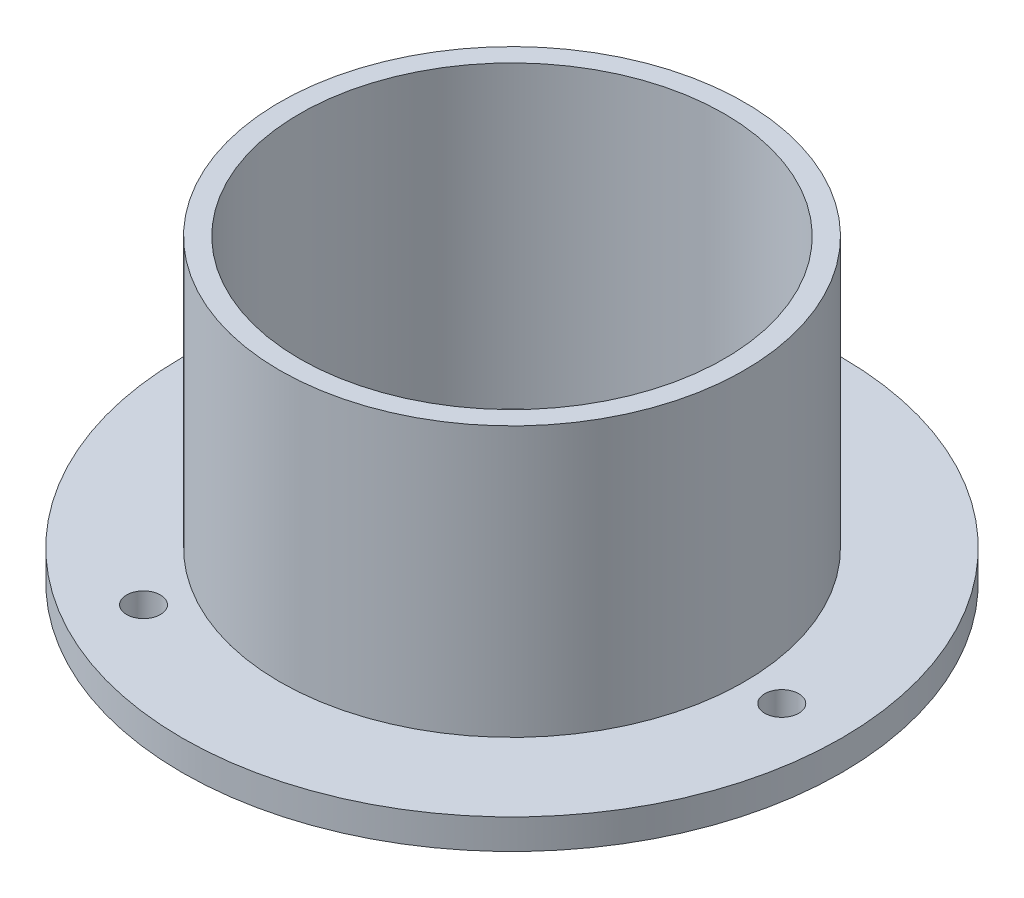
SolidWorks part; units mm, degrees
material "PETG"
ref_plane "Front Plane" through (0, 0, 0) normal (0, 0, 1) x (1, 0, 0)
ref_plane "Top Plane" through (0, 0, 0) normal (0, 1, 0) x (1, 0, 0)
ref_plane "Right Plane" through (0, 0, 0) normal (1, 0, 0) x (0, 0, -1)
sketch "Sketch1" plane through (0, 0, 0) normal (0, 1, 0) x (1, 0, 0)
  circle A2 centre (0, 0) radius 33
  circle A3 centre (0, 0) radius 21.25
  circle A4 centre (0, 0) radius 23.25
  dimension "D1" = 66
  dimension "D2" = 42.5
  dimension "D3" = 46.5
extrude "Boss-Extrude1" add sketch "Sketch1" along normal blind 30 contours A4 A3 region at (-22.5924, 0, 0)
extrude "Boss-Extrude2" add sketch "Sketch1<4>" along normal blind 3 contours A2 A4 region at (-32.0666, 0, 0)
sketch "Sketch1<4>" plane through (0, 0, 0) normal (0, 1, 0) x (1, 0, 0) same geometry as "Sketch1"
sketch "Sketch2" plane through (0, 3, 0) normal (0, 1, 0) x (1, 0, 0)
  circle A0 centre (0, 0) radius 27 construction
  circle A1 centre (27, 0) radius 1.7
  circle A2 centre (-13.5, -23.3827) radius 1.7
  circle A3 centre (0, 0) radius 27 construction
  circle A4 centre (-13.5, 23.3827) radius 1.7
  circle A5 centre (0, 0) radius 27 construction
  point P13 (0, 0)
  dimension "D1" = 54
  dimension "D2" = 3.4
  dimension "D3" = 3
extrude "Cut-Extrude1" cut sketch "Sketch2" against normal through all
equation "\"____ GENERATED PART EXPORTS ____\" = 0"
equation "\"SYS_VersionTag\" = 2"
equation "\"CDG_Enabled\" = 1"
equation "\"CDG_IsStructural\" = 0"
equation "\"CDG_FlangeThk\" = 3mm"
equation "\"CDG_MountBCDia\" = 54mm"
equation "\"CDG_MountClearDia\" = 3.4mm"
equation "\"CDG_MountCount\" = 3"
equation "\"CDG_ID\" = 42.5mm"
equation "\"CDG_WallThk\" = 2mm"
equation "\"CDG_OD\" = 46.5mm"
equation "\"CDG_SkirtLength\" = 30mm"
equation "\"CDG_ServiceSlotWidth\" = 10mm"
equation "\"CDG_ServiceSlotHeight\" = 18mm"
equation "\"CDG_ServiceSlotSectorDeg\" = 225"
equation "\"D2@Sketch1\"=\"CDG_ID\""
equation "\"D3@Sketch1\"=\"CDG_OD\""
equation "\"D1@Boss-Extrude1\"=\"CDG_SkirtLength\""
equation "\"D1@Boss-Extrude2\"=3"
equation "\"D1@Sketch2\"=\"CDG_MountBCDia\""
equation "\"D2@Sketch2\"=\"CDG_MountClearDia\""
